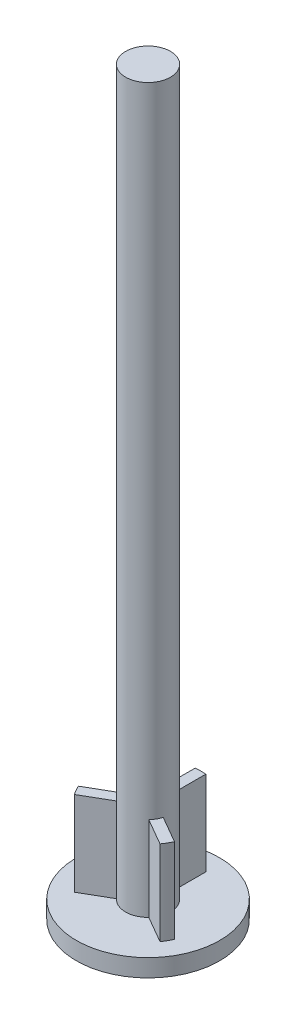
SolidWorks part; units mm, degrees
material "AISI 316 Annealed Stainless Steel Bar (SS)"
ref_plane "Front Plane" through (0, 0, 0) normal (0, 0, 1) x (1, 0, 0)
ref_plane "Top Plane" through (0, 0, 0) normal (0, 1, 0) x (1, 0, 0)
ref_plane "Right Plane" through (0, 0, 0) normal (1, 0, 0) x (0, 0, -1)
sketch "Sketch1" plane through (0, 0, 0) normal (0, 0, 1) x (1, 0, 0)
  line L0 (0, -31.8317) -> (0, 0) construction
  line L1 (0, 0) -> (10.16, 0)
  line L2 (10.16, 0) -> (10.16, 2.5)
  line L4 (3.175, 2.5) -> (3.175, 105)
  line L5 (3.175, 105) -> (0, 105)
  line L7 (0, 105) -> (0, 0)
  line L8 (10.16, 2.5) -> (3.175, 2.5)
  point P1 (3.175, 2.806)
  dimension "D1" = 10.16
  dimension "D2" = 3.175
  dimension "D3" = 2.5
  dimension "D4" = 105
revolve "Revolve1" add sketch "Sketch1" angle 360 about L0
cosmetic thread "Cosmetic Thread1" parameters "D1"=12, "D2"=5.268
sketch "Sketch2" plane through (0, 2.5, 0) normal (0, 1, 0) x (1, 0, 0)
  line L0 (-0.75, 10.1323) -> (-0.75, 0)
  line L1 (-0.75, 0) -> (0.75, 0)
  line L2 (0.75, 0) -> (0.75, 10.1323)
  circle A0 centre (0, 0) radius 10.16 construction
  arc A1 (0.75, 10.1323) -> (-0.75, 10.1323) centre (0, 0) ccw
  point P7 (0, 0)
  dimension "D1" = 1.5
extrude "Boss-Extrude1" add sketch "Sketch2" along normal blind 12
pattern_circular "CirPattern1" count 3 over 360 about axis through (0, 2.5, 0) along (0, -1, 0) of "Boss-Extrude1"
sketch "Sketch3" plane through (0, 14.5, 0) normal (0, 1, 0) x (1, 0, 0)
  circle A0 centre (0, 0) radius 7.475
  dimension "D1" = 14.95
extrude "Cut-Extrude2" cut sketch "Sketch3" against normal up to surface (12 mm away) flip side to cut up to face at (-4.5992, 2.5, -2.6553)
